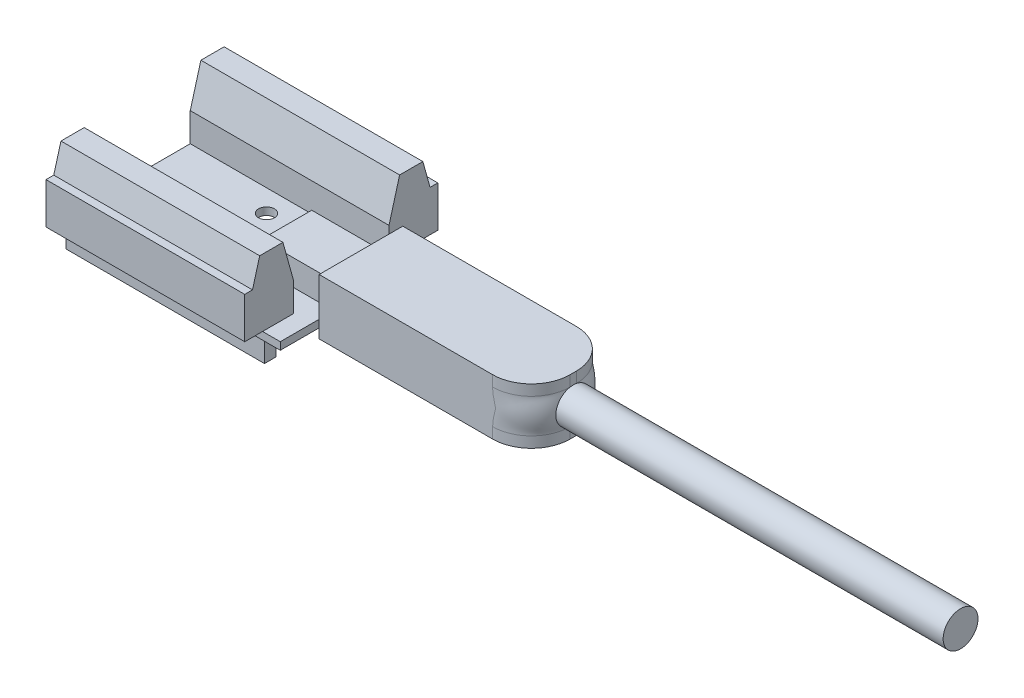
SolidWorks part; units mm, degrees
ref_plane "Front" through (0, 0, 0) normal (0, 0, 1) x (1, 0, 0)
ref_plane "Top" through (0, 0, 0) normal (0, 1, 0) x (1, 0, 0)
ref_plane "Right" through (0, 0, 0) normal (1, 0, 0) x (0, 0, -1)
sketch "Sketch2" plane through (0, 0, 0) normal (0, 1, 0) x (1, 0, 0)
  line L1 (13.97, 10.16) -> (-13.97, 10.16)
  line L2 (13.97, 10.16) -> (13.97, -10.16)
  line L3 (13.97, -10.16) -> (-13.97, -10.16)
  line L4 (-13.97, 10.16) -> (-13.97, -10.16)
  line L5 (0, -10.16) -> (0, 10.16) construction
  line L6 (13.97, 0) -> (-13.97, 0) construction
  point P0 (0, 0)
  dimension "D1" = 20.32
  dimension "D2" = 27.94
extrude "Boss-Extrude1" add sketch "Sketch2" along normal blind 0.9652
sketch "Sketch3" plane through (0, 0.9652, 0) normal (0, 1, 0) x (1, 0, 0)
  line L0 (-1.27, 3.302) -> (-1.27, -3.302) construction
  line L1 (-1.27, 0) -> (0, 0) construction
  line L2 (-13.97, 10.16) -> (-13.97, -10.16) construction
  circle A0 centre (-1.27, 3.302) radius 1.016
  circle A1 centre (-1.27, -3.302) radius 1.016
  dimension "D2" = 2.032
  dimension "D3" = 11.684
  dimension "D1" = 6.604
extrude "Cut-Extrude1" cut sketch "Sketch3" against normal through all
sketch "Sketch4" plane through (0, 0.9652, 0) normal (0, 1, 0) x (1, 0, 0)
  line L0 (13.97, -10.16) -> (13.97, 10.16) construction
  line L1 (4.624, 3.25) -> (14.224, 3.25)
  line L2 (4.624, 3.25) -> (4.624, -3.25)
  line L3 (4.624, -3.25) -> (14.224, -3.25)
  line L4 (14.224, 3.25) -> (14.224, -3.25)
  line L5 (9.424, -3.25) -> (9.424, 3.25) construction
  line L6 (4.624, 0) -> (14.224, 0) construction
  point P140 (9.424, 0)
  dimension "D1" = 0.254
  dimension "D2" = 9.6
  dimension "D3" = 6.5
extrude "Boss-Extrude2" add sketch "Sketch4" along normal blind 3.32
sketch "Sketch5" plane through (-13.97, 0, 0) normal (-1, 0, 0) x (0, 0, 1)
  line L0 (-6.16, 0.9652) -> (-12.46, 0.9652)
  line L1 (-10.16, 0.9652) -> (10.16, 0.9652) construction
  line L2 (-12.46, 0.9652) -> (-12.46, 6.2652)
  line L3 (-12.46, 6.2652) -> (-11.46, 6.2652)
  line L4 (-11.46, 6.2652) -> (-10.5317, 9.6152)
  line L5 (-10.5317, 9.6152) -> (-7.5317, 9.6152)
  line L6 (-7.5317, 9.6152) -> (-6.16, 4.6652)
  line L7 (-6.16, 4.6652) -> (-6.16, 0.9652)
  line L8 (-9.0317, 9.6152) -> (-9.0317, 0.9652) construction
  line L9 (-10.16, 0.9652) -> (-10.16, 0) construction
  line L10 (0, 0) -> (0, 4.2852) construction
  line L11 (-3.25, 4.2852) -> (3.25, 4.2852) construction
  line L12 (9.0317, 9.6152) -> (9.0317, 0.9652) construction
  line L13 (6.16, 4.6652) -> (6.16, 0.9652)
  line L14 (7.5317, 9.6152) -> (6.16, 4.6652)
  line L15 (10.5317, 9.6152) -> (7.5317, 9.6152)
  line L16 (11.46, 6.2652) -> (10.5317, 9.6152)
  line L17 (12.46, 6.2652) -> (11.46, 6.2652)
  line L18 (12.46, 0.9652) -> (12.46, 6.2652)
  line L19 (6.16, 0.9652) -> (12.46, 0.9652)
  point P16 (-10.16, 0.4826)
  dimension "D1" = 6.3
  dimension "D2" = 5.3
  dimension "D3" = 8.65
  dimension "D4" = 1
  dimension "D5" = 3.7
  dimension "D6" = 2.3
  dimension "D7" = 3
extrude "Boss-Extrude3" add sketch "Sketch5" against normal blind 25.654
sketch "Sketch6" plane through (-13.97, 0, 0) normal (-1, 0, 0) x (0, 0, 1)
  line L0 (-10.16, 0) -> (10.16, 0) construction
  line L1 (-8.41, 0) -> (-9.91, 0)
  line L2 (-8.41, 0) -> (-8.41, -2.75)
  line L3 (-8.41, -2.75) -> (-9.91, -2.75)
  line L4 (-9.91, 0) -> (-9.91, -2.75)
  line L5 (-9.16, -2.75) -> (-9.16, 0) construction
  line L6 (-8.41, -1.375) -> (-9.91, -1.375) construction
  line L7 (-10.16, 0.9652) -> (-10.16, 0) construction
  line L8 (0, 0) -> (0, 4.2852) construction
  line L9 (-3.25, 4.2852) -> (3.25, 4.2852) construction
  line L10 (8.41, -1.375) -> (9.91, -1.375) construction
  line L11 (9.16, -2.75) -> (9.16, 0) construction
  line L12 (9.91, 0) -> (9.91, -2.75)
  line L13 (8.41, -2.75) -> (9.91, -2.75)
  line L14 (8.41, 0) -> (8.41, -2.75)
  line L15 (8.41, 0) -> (9.91, 0)
  point P20 (9.16, -1.375)
  point P136 (-9.16, -1.375)
  dimension "D1" = 1
  dimension "D2" = 1.5
  dimension "D3" = 2.75
extrude "Boss-Extrude4" add sketch "Sketch6" against normal blind 25.654
sketch "Sketch7" plane through (14.224, 0, 0) normal (1, 0, 0) x (0, 0, -1)
  line L0 (-3.25, 4.2852) -> (3.25, 0.9652) construction
  line L1 (-5.4, -0.9748) -> (5.4, -0.9748)
  line L2 (-5.4, -0.9748) -> (-5.4, 6.2252)
  line L3 (-5.4, 6.2252) -> (5.4, 6.2252)
  line L4 (5.4, -0.9748) -> (5.4, 6.2252)
  line L5 (0, 6.2252) -> (0, -0.9748) construction
  line L6 (-5.4, 2.6252) -> (5.4, 2.6252) construction
  point P0 (0, 2.6252)
  dimension "D1" = 7.2
  dimension "D2" = 10.8
extrude "Boss-Extrude5" add sketch "Sketch7" along normal blind 27.4
sketch "Sketch8" plane through (41.624, 0, 0) normal (1, 0, 0) x (0, 0, -1)
  circle A0 centre (0, 2.6252) radius 2.25
  dimension "D1" = 4.5
extrude "Boss-Extrude6" add sketch "Sketch8" along normal blind 50
fillet "Fillet1" radius 5 2 edges at (41.624, 2.6252, -5.4) (41.624, 2.6252, 5.4)
